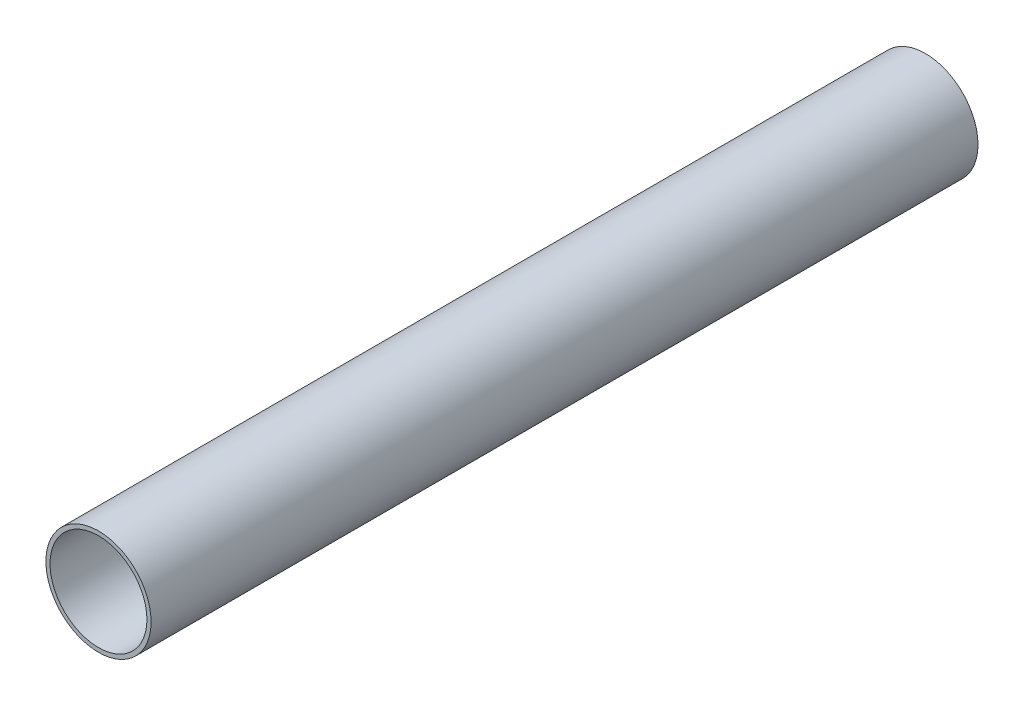
SolidWorks part; units mm, degrees
ref_plane "Front Plane" through (0, 0, 0) normal (0, 0, 1) x (1, 0, 0)
ref_plane "Top Plane" through (0, 0, 0) normal (0, 1, 0) x (1, 0, 0)
ref_plane "Right Plane" through (0, 0, 0) normal (1, 0, 0) x (0, 0, -1)
sketch "Sketch1" plane through (0, 0, 0) normal (0, 0, 1) x (1, 0, 0)
  circle A0 centre (0, 0) radius 15.9
  circle A1 centre (0, 0) radius 14.65
  dimension "D1" = 31.8
  dimension "D2" = 29.3
extrude "Boss-Extrude1" add sketch "Sketch1" against normal blind 250
